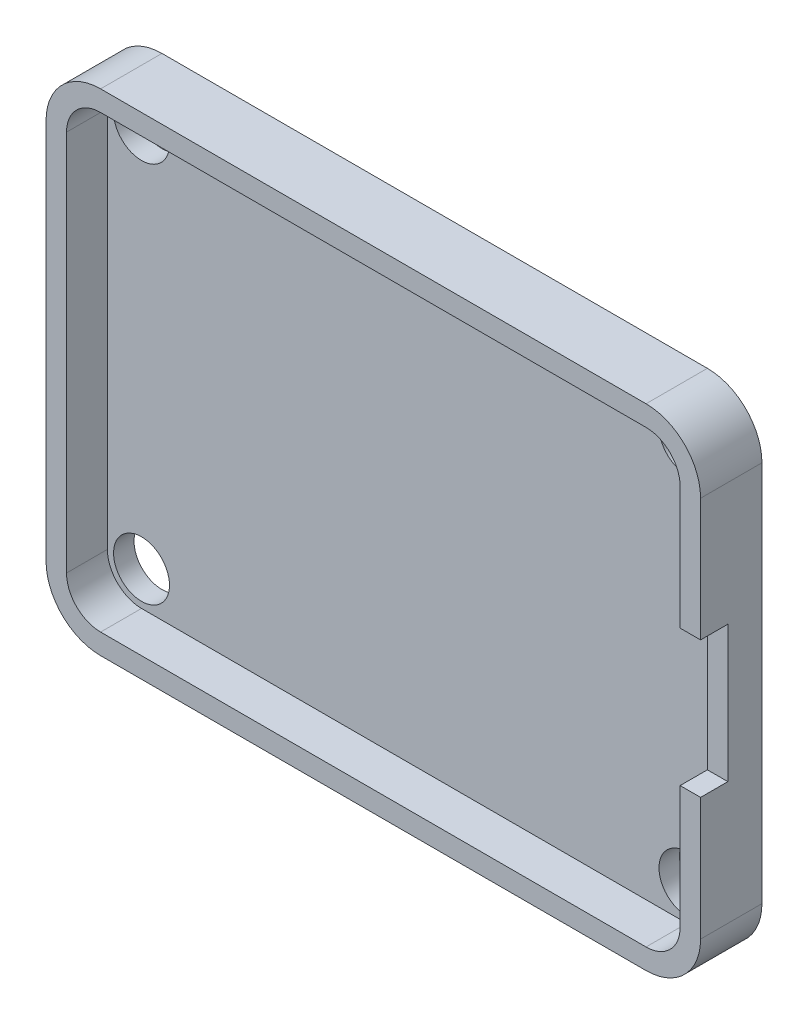
SolidWorks part; units mm, degrees
ref_plane "Front Plane" through (0, 0, 0) normal (0, 0, 1) x (1, 0, 0)
ref_plane "Top Plane" through (0, 0, 0) normal (0, 1, 0) x (1, 0, 0)
ref_plane "Right Plane" through (0, 0, 0) normal (1, 0, 0) x (0, 0, -1)
sketch "Sketch1" plane through (0, 0, 0) normal (0, 0, 1) x (1, 0, 0)
  line L1 (-20, -18) -> (20, -18)
  line L2 (-24, -14) -> (-24, 14)
  line L3 (-20, 18) -> (20, 18)
  line L4 (24, -14) -> (24, 14)
  line L5 (-24, -18) -> (24, 18) construction
  line L6 (-24, 18) -> (24, -18) construction
  arc A0 (-24, -14) -> (-20, -18) centre (-20, -14) ccw
  arc A1 (20, -18) -> (24, -14) centre (20, -14) ccw
  arc A2 (24, 14) -> (20, 18) centre (20, 14) ccw
  arc A3 (-20, 18) -> (-24, 14) centre (-20, 14) ccw
  circle A4 centre (-20, -14) radius 2.05
  circle A5 centre (-20, 14) radius 2.05
  circle A6 centre (20, 14) radius 2.05
  circle A7 centre (20, -14) radius 2.05
  point P0 (0, 0)
  dimension "D3" = 4
  dimension "D4" = 4
  dimension "D5" = 4
  dimension "D6" = 4
  dimension "D7" = 4.1
  dimension "D8" = 4.1
  dimension "D9" = 4.1
  dimension "D10" = 4.1
  dimension "D1" = 48
  dimension "D2" = 36
extrude "Boss-Extrude1" add sketch "Sketch1" along normal mid plane 4.5
sketch "Sketch3" plane through (0, 0, 2.25) normal (0, 0, 1) x (1, 0, 0)
  line L30 (22.5, -14) -> (22.5, 14)
  line L31 (20, 16.5) -> (-20, 16.5)
  line L32 (-22.5, 14) -> (-22.5, -14)
  line L33 (-20, -16.5) -> (20, -16.5)
  line L34 (22.5, -14) -> (22.5, 14)
  line L35 (20, 16.5) -> (-20, 16.5)
  line L36 (-22.5, 14) -> (-22.5, -14)
  line L37 (-20, -16.5) -> (20, -16.5)
  arc A24 (20, -16.5) -> (22.5, -14) centre (20, -14) ccw
  arc A25 (22.5, 14) -> (20, 16.5) centre (20, 14) ccw
  arc A26 (-20, 16.5) -> (-22.5, 14) centre (-20, 14) ccw
  arc A27 (-22.5, -14) -> (-20, -16.5) centre (-20, -14) ccw
  arc A28 (20, -16.5) -> (22.5, -14) centre (20, -14) ccw
  arc A29 (22.5, 14) -> (20, 16.5) centre (20, 14) ccw
  arc A30 (-20, 16.5) -> (-22.5, 14) centre (-20, 14) ccw
  arc A31 (-22.5, -14) -> (-20, -16.5) centre (-20, -14) ccw
  dimension "D1" = 1.5
extrude "Cut-Extrude2" cut sketch "Sketch3" against normal offset from surface (3 mm away) 1.5 up to face at (22.05, 14, -2.25)
sketch "Sketch5" plane through (0, 0, 2.25) normal (0, 0, 1) x (1, 0, 0)
  line L0 (24, -14) -> (24, 14) construction
  line L1 (19, -5) -> (29, -5)
  line L2 (19, -5) -> (19, 5)
  line L3 (19, 5) -> (29, 5)
  line L4 (29, -5) -> (29, 5)
  line L5 (19, -5) -> (29, 5) construction
  line L6 (19, 5) -> (29, -5) construction
  point P0 (24, 0)
  dimension "D1" = 10
  dimension "D2" = 10
extrude "Cut-Extrude4" cut sketch "Sketch5" against normal blind 2
